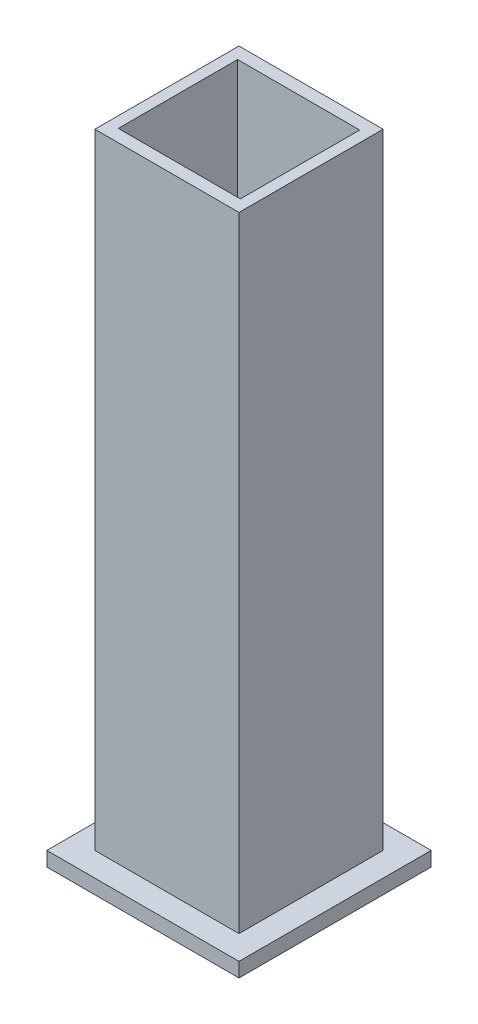
SolidWorks part; units mm, degrees
ref_plane "Alzado" through (0, 0, 0) normal (0, 0, 1) x (1, 0, 0)
ref_plane "Planta" through (0, 0, 0) normal (0, 1, 0) x (1, 0, 0)
ref_plane "Vista lateral" through (0, 0, 0) normal (1, 0, 0) x (0, 0, -1)
sketch "Croquis1" plane through (0, 0, 0) normal (0, 1, 0) x (1, 0, 0)
  line L1 (-20, 20) -> (20, 20)
  line L2 (-20, 20) -> (-20, -20)
  line L3 (-20, -20) -> (20, -20)
  line L4 (20, 20) -> (20, -20)
  line L5 (-20, 20) -> (20, -20) construction
  line L6 (-20, -20) -> (20, 20) construction
  point P0 (0, 0)
  dimension "D1" = 40
  dimension "D2" = 40
extrude "Saliente-Extruir1" add sketch "Croquis1" along normal blind 3
sketch "Croquis2" plane through (0, 3, 0) normal (0, 1, 0) x (1, 0, 0)
  line L1 (-15, 15) -> (15, 15)
  line L2 (-15, 15) -> (-15, -15)
  line L3 (-15, -15) -> (15, -15)
  line L4 (15, 15) -> (15, -15)
  line L5 (-15, 15) -> (15, -15) construction
  line L6 (-15, -15) -> (15, 15) construction
  line L7 (-10.2121, 10.2121) -> (10.2121, 10.2121)
  line L8 (-10.2121, 10.2121) -> (-10.2121, -10.2121)
  line L9 (-10.2121, -10.2121) -> (10.2121, -10.2121)
  line L10 (10.2121, 10.2121) -> (10.2121, -10.2121)
  line L11 (-10.2121, 10.2121) -> (10.2121, -10.2121) construction
  line L12 (-10.2121, -10.2121) -> (10.2121, 10.2121) construction
  point P0 (0, 0)
  point P6 (0, 0)
  dimension "D1" = 30
  dimension "D2" = 30
extrude "Saliente-Extruir2" add sketch "Croquis2" along normal blind 130
sketch "Croquis3" plane through (0, 133, 0) normal (0, 1, 0) x (1, 0, 0)
  line L1 (12.7044, 12.414) -> (-12.7044, 12.414)
  line L2 (12.7044, 12.414) -> (12.7044, -12.414)
  line L3 (12.7044, -12.414) -> (-12.7044, -12.414)
  line L4 (-12.7044, 12.414) -> (-12.7044, -12.414)
  line L5 (12.7044, 12.414) -> (-12.7044, -12.414) construction
  line L6 (12.7044, -12.414) -> (-12.7044, 12.414) construction
  point P0 (0, 0)
extrude "Cortar-Extruir1" cut sketch "Croquis3" against normal blind 30
